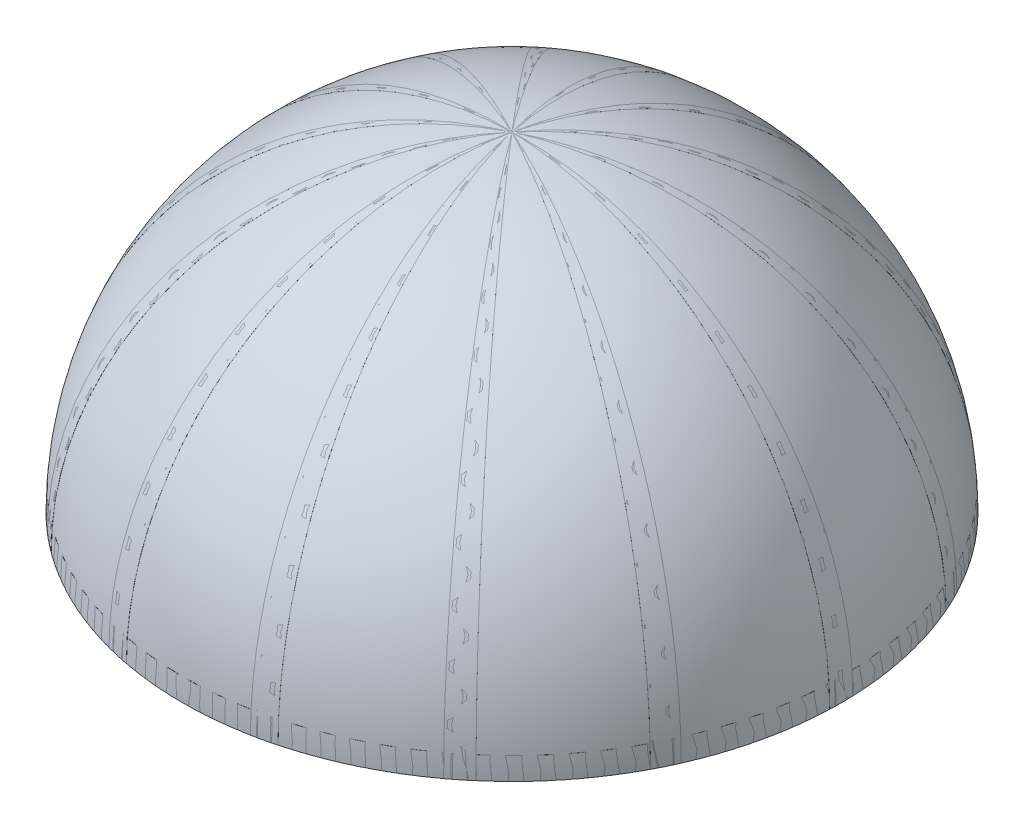
SolidWorks part; units mm, degrees
note: '?' marks a value the reader was unsure of.
ref_plane "Front Plane" through (0, 0, 0) normal (0, 0, 1) x (1, 0, 0)
ref_plane "Top Plane" through (0, 0, 0) normal (0, 1, 0) x (1, 0, 0)
ref_plane "Right Plane" through (0, 0, 0) normal (1, 0, 0) x (0, 0, -1)
ref_axis "X-Axis" through (-82.5, 0, 0) along (1, 0, 0)?
ref_axis "Z-Axis" through (0, 77.3482, 0) along (0, -1, 0)?
ref_axis "Y-Axis" through (0, 0, 82.5) along (0, 0, -1)?
sketch3d "Construction lines"
  line L0 (0, 0, 82.5) -> (0, 0, -82.5) construction
  circle A0 centre (0, 0, 0) radius 75 construction
  circle A1 centre (0, 0, 0) radius 71 construction
  circle A2 centre (0, 0, 0) radius 71 construction
  circle A3 centre (0, 0, 0) radius 75 construction
  circle A4 centre (0, 0, 0.6198) radius 75 construction
  circle A5 centre (0, 0, 0) radius 71 construction
  point P2 (0, 75, 0)
  point P5 (0, 71, 0)
  point P7 (0, 0, 71)
  point P10 (0, 0, 75)
  point P12 (75, 0, 0.6198)
  point P16 (71, 0, 0)
  point P18 (0, 0, 0)
  dimension "D1" = 150
  dimension "D2" = 4
sketch "Sketch9" plane through (0, 0, 0) normal (0, 1, 0) x (1, 0, 0)
  line L0 (0, 75) -> (0, 71)
  line L1 (0, -71) -> (0, -75)
  arc A0 (0, 75) -> (0, -75) centre (0, 0) ccw
  arc A1 (0, 71) -> (0, -71) centre (0, 0) ccw
  dimension "D1" = 75
  dimension "D2" = 71
revolve "Shell" add sketch "Sketch9" angle 180 about L0
sketch "Sketch4" plane through (0, 0, 0) normal (0, 0, 1) x (1, 0, 0)
  line L0 (-75, 0) -> (-71, 0)
  line L1 (-70.8237, 5) -> (-74.8331, 5)
  line L2 (0, 0) -> (0, 10) construction
  arc A0 (-74.8331, 5) -> (-75, 0) centre (0, 0) ccw
  arc A1 (-70.8237, 5) -> (-71, 0) centre (0, 0) ccw
  dimension "D1" = 75
  dimension "D2" = 71
  dimension "D3" = 5
revolve "Base" add sketch "Sketch4" angle 360 about L2
sketch "Sketch10" plane through (0, 0, 0) normal (0, 0, 1) x (1, 0, 0)
  line L0 (-75, 0) -> (-71, 0)
  line L1 (0, 75) -> (0, 71)
  arc A2 (0, 75) -> (-75, 0) centre (0, 0) ccw
  circle A3 centre (0, 0) radius 75 construction
  arc A4 (0, 71) -> (-71, 0) centre (0, 0) ccw
  circle A5 centre (0, 0) radius 71 construction
revolve "Revolve1" add sketch "Sketch10" angle 2 about axis through (0, 77.3482, 0) along (0, -1, 0)
pattern_circular "CirPattern1" count 14 over 360 about axis through (0, 0, 0) along (0, 1, 0) of bodies 675
sketch "Sketch12" plane through (0, 0, 0) normal (0, 1, 0) x (1, 0, 0)
  line L0 (-82.5, 0) -> (82.5, 0) construction
  line L1 (-75, 0) -> (0, 0)
  line L2 (0, 0) -> (-67.4952, -32.7017)
  arc A0 (-75, 0) -> (-67.4952, -32.7017) centre (0, 0) ccw
  circle A1 centre (0, 0) radius 75 construction
equation "\"wall_thickness\"= 1"
equation "\"radius\"= 75mm"
equation "\"shell_thickness\"= 4mm"
equation "\"D1@Sketch9\"=\"radius\""
equation "\"D2@Sketch9\"=\"radius\"-\"shell_thickness\""
equation "\"D1@Sketch4\"=\"radius\""
equation "\"D2@Sketch4\"=\"radius\"-\"shell_thickness\""
equation "\"base_height\"= 5mm"
equation "\"D3@Sketch4\"=\"base_height\""
equation "\"edge_scribed\"= \"radius\" * 1.0044063878192154002"
equation "\"D1@Construction lines\"=\"radius\"*2"
equation "\"D2@Construction lines\"=\"shell_thickness\""
